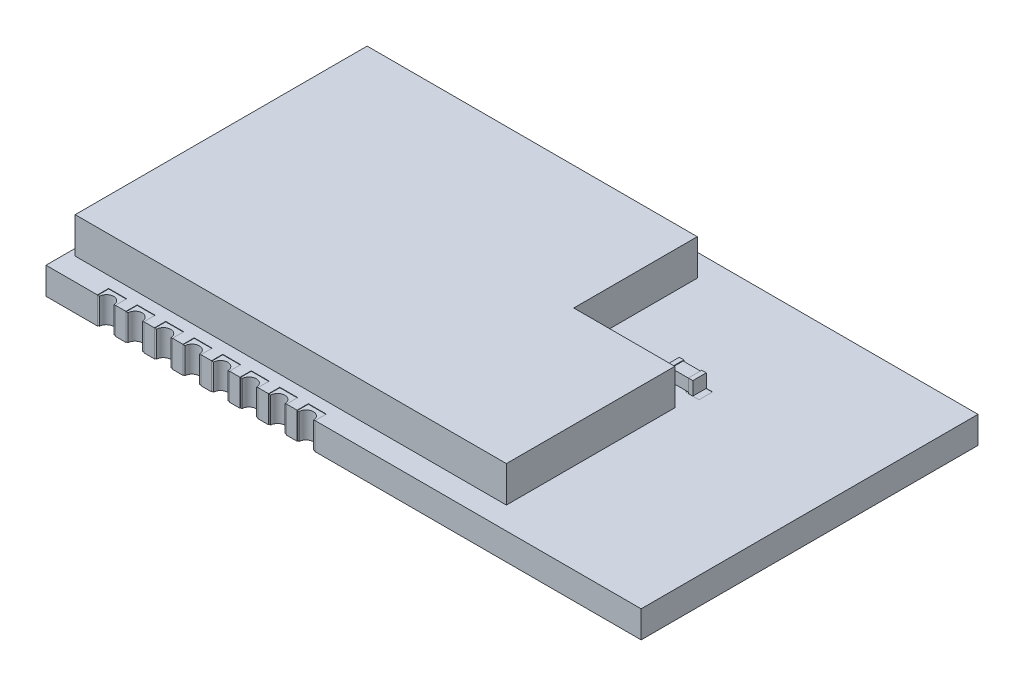
SolidWorks part; units mm, degrees
other "相机1"
ref_plane "前视基准面" through (0, 0, 0) normal (0, 0, 1) x (1, 0, 0)
ref_plane "上视基准面" through (0, 0, 0) normal (0, 1, 0) x (1, 0, 0)
ref_plane "右视基准面" through (0, 0, 0) normal (1, 0, 0) x (0, 0, -1)
sketch "草图1" plane through (0, 0, 0) normal (0, 1, 0) x (1, 0, 0)
  line L1 (0, 15) -> (26.5, 15)
  line L2 (0, 15) -> (0, 0)
  line L3 (0, 0) -> (26.5, 0)
  line L4 (26.5, 15) -> (26.5, 0)
  line L5 (0, 15) -> (26.5, 0) construction
  line L6 (0, 0) -> (26.5, 15) construction
  point P0 (13.25, 7.5)
extrude "凸台-拉伸1" add sketch "草图1" along normal blind 1.2
sketch "草图2" plane through (0, 1.2, 0) normal (0, 1, 0) x (1, 0, 0)
  line L0 (0.3, 1) -> (19.5, 1)
  line L2 (0.3, 1) -> (0.3, 14)
  line L3 (0.3, 14) -> (15, 14)
  line L4 (15, 8.5) -> (15, 14)
  line L7 (15, 8.5) -> (19.5, 8.5)
  line L8 (19.5, 1) -> (19.5, 8.5)
extrude "凸台-拉伸2" add sketch "草图2" along normal blind 1.6
sketch "草图3" plane through (0, 1.2, 0) normal (0, 1, 0) x (1, 0, 0)
  line L0 (0, 0) -> (26.5, 0) construction
  line L1 (2.365, 0) -> (3.015, 0)
  line L2 (3.635, 0) -> (4.285, 0)
  line L3 (4.905, 0) -> (5.555, 0)
  line L4 (6.175, 0) -> (6.825, 0)
  line L5 (7.445, 0) -> (8.095, 0)
  line L6 (8.715, 0) -> (9.365, 0)
  line L7 (9.985, 0) -> (10.635, 0)
  line L8 (11.255, 0) -> (11.905, 0)
  arc A0 (3.015, 0) -> (2.365, 0) centre (2.69, 0) ccw
  arc A1 (4.285, 0) -> (3.635, 0) centre (3.96, 0) ccw
  arc A2 (5.555, 0) -> (4.905, 0) centre (5.23, 0) ccw
  arc A3 (6.825, 0) -> (6.175, 0) centre (6.5, 0) ccw
  arc A4 (8.095, 0) -> (7.445, 0) centre (7.77, 0) ccw
  arc A5 (9.365, 0) -> (8.715, 0) centre (9.04, 0) ccw
  arc A6 (10.635, 0) -> (9.985, 0) centre (10.31, 0) ccw
  arc A7 (11.905, 0) -> (11.255, 0) centre (11.58, 0) ccw
  dimension "D1" = 8
ref_plane "基准面4" through (0, 0, -7.5) normal (0, 0, -1) x (-1, 0, 0)
extrude "切除-拉伸1" cut sketch "草图3" against normal blind 1.6
mirror "镜向1" about plane through (0, 0, -7.5) normal (0, 0, -1) of "切除-拉伸1"
sketch "草图4" plane through (0, 1.2, 0) normal (0, 1, 0) x (1, 0, 0)
  line L1 (18.25, 9.35) -> (19.45, 9.35)
  line L2 (18.25, 9.35) -> (18.25, 9.95)
  line L3 (18.25, 9.95) -> (19.45, 9.95)
  line L4 (19.45, 9.35) -> (19.45, 9.95)
  line L5 (18.25, 9.35) -> (19.45, 9.95) construction
  line L6 (18.25, 9.95) -> (19.45, 9.35) construction
  point P0 (18.85, 9.65)
extrude "凸台-拉伸3" add sketch "草图4" along normal blind 0.6
ref_plane "基准面5" through (2.365, 1.2, 0) normal (1, 0, 0) x (0, 0, -1)
sketch "草图6" plane through (0, 1.2, 0) normal (0, 1, 0) x (1, 0, 0)
  line L0 (3.015, 0) -> (3.635, 0) construction
  line L2 (2.29, 0) -> (2.29, 0.5)
  line L3 (2.29, 0.5) -> (3.09, 0.5)
  line L4 (3.09, 0) -> (3.09, 0.5)
  line L7 (0, 0) -> (2.365, 0) construction
  line L8 (3.015, 0) -> (3.09, 0)
  line L9 (2.29, 0) -> (2.365, 0)
  arc A0 (3.015, 0) -> (2.365, 0) centre (2.69, 0) ccw construction
  arc A1 (3.015, 0) -> (2.365, 0) centre (2.69, 0) ccw
extrude "切除-拉伸2" cut sketch "草图6" against normal blind 0.02
sketch "草图9" plane through (0, 0, 0) normal (0, -1, 0) x (1, 0, 0)
  line L0 (0, 0) -> (2.365, 0) construction
  line L1 (3.015, 0) -> (3.635, 0) construction
  line L2 (2.29, 0) -> (2.365, 0)
  line L3 (3.015, 0) -> (3.09, 0)
  line L6 (2.29, 0) -> (2.29, -1)
  line L7 (2.29, -1) -> (3.09, -1)
  line L8 (3.09, 0) -> (3.09, -1)
  arc A0 (2.365, 0) -> (3.015, 0) centre (2.69, 0) ccw construction
  arc A1 (2.365, 0) -> (3.015, 0) centre (2.69, 0) ccw
extrude "切除-拉伸3" cut sketch "草图9" against normal blind 0.02
sketch "草图8" plane through (0, 0, 0) normal (0, 0, 1) x (1, 0, 0)
  line L0 (0, 0) -> (2.29, 0) construction
  line L1 (3.09, 1.2) -> (2.29, 1.2)
  line L2 (3.09, 1.2) -> (3.09, 0)
  line L3 (3.09, 0) -> (2.29, 0)
  line L4 (2.29, 1.2) -> (2.29, 0)
extrude "切除-拉伸4" cut sketch "草图8" against normal blind 0.01
mirror "镜向2" about plane through (0, 0, -7.5) normal (0, 0, -1) of "切除-拉伸4", "切除-拉伸3", "切除-拉伸2"
pattern_linear "阵列(线性)1" count 8 spacing 1.27 along (1, 0, 0) of "切除-拉伸2", "切除-拉伸3", "切除-拉伸4", "镜向2"
sketch "草图10" plane through (0, 1.2, 0) normal (0, 1, 0) x (1, 0, 0)
  line L0 (16.9801, 9.3514) -> (17.5801, 9.3514)
  line L1 (17.5801, 9.3514) -> (17.5801, 9.9514)
  line L2 (17.5801, 9.9514) -> (16.9801, 9.9514)
  line L3 (16.9801, 9.9514) -> (16.9801, 9.3514)
  line L4 (17.9187, 9.3514) -> (18.6537, 9.3514)
  line L5 (18.6537, 9.3514) -> (18.6537, 9.9514)
  line L6 (18.6537, 9.9514) -> (17.9187, 9.9514)
  line L7 (17.9187, 9.9514) -> (17.9187, 9.3514)
  line L8 (19.1274, 9.3514) -> (19.7274, 9.3514)
  line L9 (19.7274, 9.3514) -> (19.7274, 9.9514)
  line L10 (19.7274, 9.9514) -> (19.1274, 9.9514)
  line L11 (19.1274, 9.9514) -> (19.1274, 9.3514)
extrude "切除-拉伸5" cut sketch "草图10" against normal blind 0.01
sketch "草图11" plane through (0, 1.8, 0) normal (0, 1, 0) x (1, 0, 0)
  line L1 (18.45, 9.95) -> (19.25, 9.95)
  line L2 (18.45, 9.95) -> (18.45, 9.35)
  line L3 (18.45, 9.35) -> (19.25, 9.35)
  line L4 (19.25, 9.95) -> (19.25, 9.35)
  line L5 (18.45, 9.95) -> (19.25, 9.35) construction
  line L6 (18.45, 9.35) -> (19.25, 9.95) construction
  point P0 (18.85, 9.65)
extrude "切除-拉伸6" cut sketch "草图11" against normal blind 0.03
ref_point "点1"
ref_axis "基准轴1" through (18.25, 1.5, -9.65) along (1, 0, 0)
pattern_circular "阵列(圆周)1" count 4 every 90 about axis through (18.25, 1.5, -9.65) along (1, 0, 0) of "切除-拉伸6"
